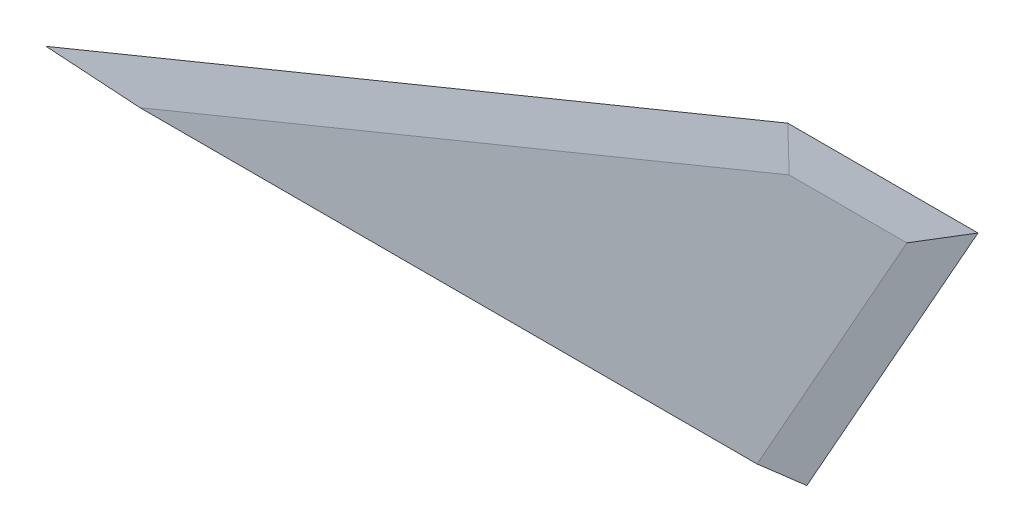
SolidWorks part; units mm, degrees
material "Thornel Mat VMA"
ref_plane "Front Plane" through (0, 0, 0) normal (0, 0, 1) x (1, 0, 0)
ref_plane "Top Plane" through (0, 0, 0) normal (0, 1, 0) x (1, 0, 0)
ref_plane "Right Plane" through (0, 0, 0) normal (1, 0, 0) x (0, 0, -1)
sketch "Sketch1" plane through (0, 0, 0) normal (0, 0, 1) x (1, 0, 0)
  line L0 (0, 0) -> (200, 0)
  line L1 (200, 0) -> (245, 80.01)
  line L2 (245, 80.01) -> (195, 80.01)
  line L3 (195, 80.01) -> (0, 0)
  dimension "D1" = 200
  dimension "D2" = 50
  dimension "D3" = 195
  dimension "D4" = 80.01
extrude "Boss-Extrude1" add sketch "Sketch1" along normal blind 3.18
chamfer "Chamfer1" distance 1.59 distance2 10 3 edges at (222.5, 40.005, 3.18) (97.5, 40.005, 3.18) (220, 80.01, 3.18) first distance on face at (222.5, 40.005, 1.59) first distance on face at (97.5, 40.005, 1.59) first distance on face at (220, 80.01, 1.59)
chamfer "Chamfer2" distance 10 distance2 1.59 3 edges at (222.5, 40.005, 0) (97.5, 40.005, 0) (220, 80.01, 0) first distance on face at (160, 40.005, 0)
sketch "Sketch2" plane through (0, 0, 0) normal (1, 0, 0) x (0, 0, -1)
  circle A0 centre (-1.59, -40.9692) radius 41
  dimension "D1" = 82
extrude "Cut-Extrude1" cut sketch "Sketch2" along normal blind 200
